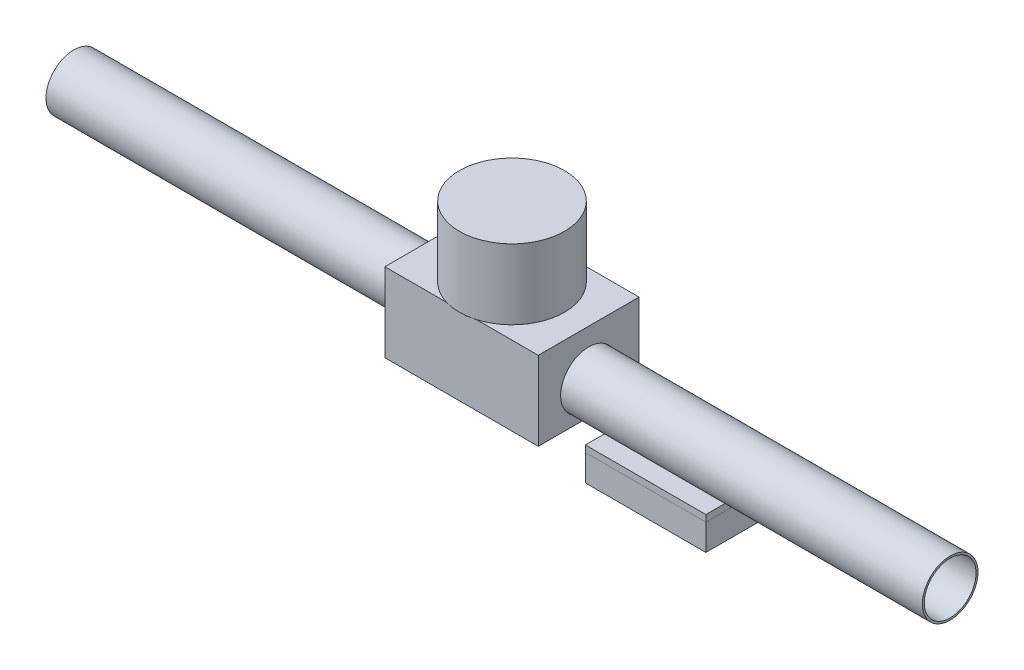
SolidWorks part; units mm, degrees
ref_plane "Front Plane" through (0, 0, 0) normal (0, 0, 1) x (1, 0, 0)
ref_plane "Top Plane" through (0, 0, 0) normal (0, 1, 0) x (1, 0, 0)
ref_plane "Right Plane" through (0, 0, 0) normal (1, 0, 0) x (0, 0, -1)
sketch "Sketch1" plane through (0, 0, 0) normal (1, 0, 0) x (0, 0, -1)
  circle A0 centre (0, 0) radius 12.7
  circle A1 centre (0, 0) radius 11.811
extrude "Boom" add sketch "Sketch1" along normal mid plane 400 separate body
sketch "Sketch2" plane through (0, 0, 0) normal (1, 0, 0) x (0, 0, -1)
  line L1 (-23, -15) -> (23, -15)
  line L2 (-23, -15) -> (-23, 21)
  line L3 (-23, 21) -> (23, 21)
  line L4 (23, -15) -> (23, 21)
  circle A0 centre (0, 0) radius 12.8
extrude "Mount" add sketch "Sketch2" along normal mid plane 70 separate body
sketch "Sketch3" plane through (0, 0, 0) normal (0, 1, 0) x (1, 0, 0)
  circle A0 centre (0, 0) radius 24
extrude "Motor" add sketch "Sketch3" along normal blind 32 from offset 21 separate body
sketch "Sketch4" plane through (0, 0, 0) normal (0, 1, 0) x (1, 0, 0)
  line L1 (47.5, -14) -> (102.5, -14)
  line L2 (47.5, -14) -> (47.5, 14)
  line L3 (47.5, 14) -> (102.5, 14)
  line L4 (102.5, -14) -> (102.5, 14)
extrude "Pad" add sketch "Sketch4" against normal blind 3 from offset 12.7 separate body offset against normal yes
sketch "Sketch5" plane through (0, 0, 0) normal (0, 1, 0) x (1, 0, 0)
  line L1 (47.5, -14) -> (102.5, -14)
  line L2 (47.5, -14) -> (47.5, 14)
  line L3 (47.5, 14) -> (102.5, 14)
  line L4 (102.5, -14) -> (102.5, 14)
extrude "ESC" add sketch "Sketch5" against normal blind 12 from offset 15.7 separate body
